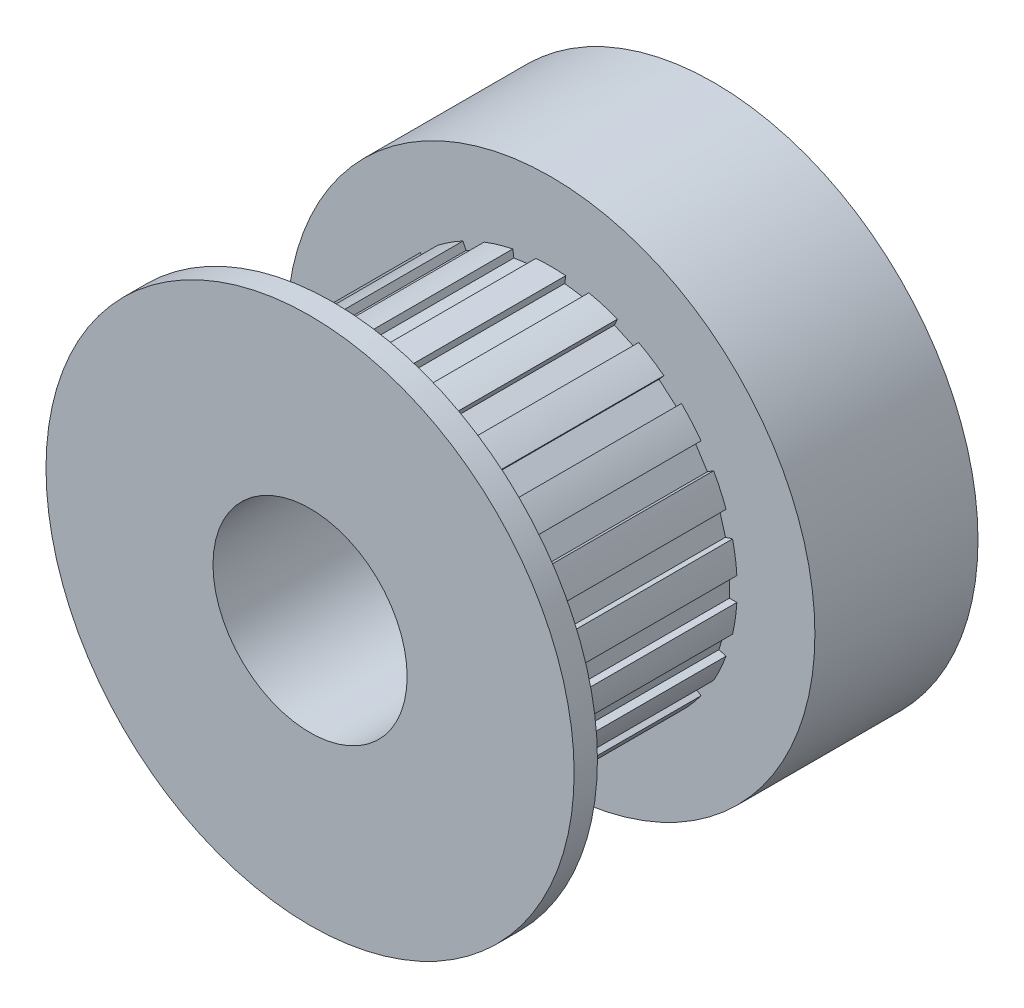
SolidWorks part; units mm, degrees
ref_plane "Front Plane" through (0, 0, 0) normal (0, 0, 1) x (1, 0, 0)
ref_plane "Top Plane" through (0, 0, 0) normal (0, 1, 0) x (1, 0, 0)
ref_plane "Right Plane" through (0, 0, 0) normal (1, 0, 0) x (0, 0, -1)
sketch "Sketch1" plane through (0, 0, 0) normal (0, 0, 1) x (1, 0, 0)
  circle A0 centre (0, 0) radius 8.636
  dimension "D1" = 17.272
extrude "Boss-Extrude1" add sketch "Sketch1" against normal blind 0.762
sketch "Sketch2" plane through (0, 0, -0.762) normal (0, 0, -1) x (-1, 0, 0)
  circle A0 centre (0, 0) radius 6.096
  dimension "D1" = 12.192
extrude "Boss-Extrude2" add sketch "Sketch2" along normal blind 7.112
sketch "Sketch3" plane through (0, 0, -7.874) normal (0, 0, -1) x (-1, 0, 0)
  circle A0 centre (0, 0) radius 8.636
  dimension "D1" = 17.272
extrude "Boss-Extrude3" add sketch "Sketch3" along normal blind 5.334
sketch "Sketch4" plane through (0, 0, 0) normal (0, 0, 1) x (1, 0, 0)
  circle A0 centre (0, 0) radius 3.175
  dimension "D1" = 6.35
extrude "Cut-Extrude1" cut sketch "Sketch4" against normal blind 25.654
ref_plane "Plane2" through (-6.096, 0, 0) normal (-1, 0, 0) x (0, 0, 1)
sketch "Sketch5" plane through (-6.096, 0, 0) normal (-1, 0, 0) x (0, 0, 1)
  line L0 (-7.874, -6.096) -> (-7.874, 6.096) construction
  line L1 (-7.874, 0.381) -> (-0.762, 0.381)
  line L2 (-7.874, 0.381) -> (-7.874, -0.381)
  line L3 (-7.874, -0.381) -> (-0.762, -0.381)
  line L4 (-0.762, 0.381) -> (-0.762, -0.381)
  line L5 (-0.762, 6.096) -> (-0.762, -6.096) construction
  point P8 (-7.874, 0)
  dimension "D1" = 0.762
extrude "Cut-Extrude2" cut sketch "Sketch5" against normal blind 0.254
ref_axis "Axis1" through (0, 0, -13.208) along (0, 0, 1)
pattern_circular "CirPattern1" count 22 over 360 about axis through (0, 0, -13.208) along (0, 0, 1) of "Cut-Extrude2"
